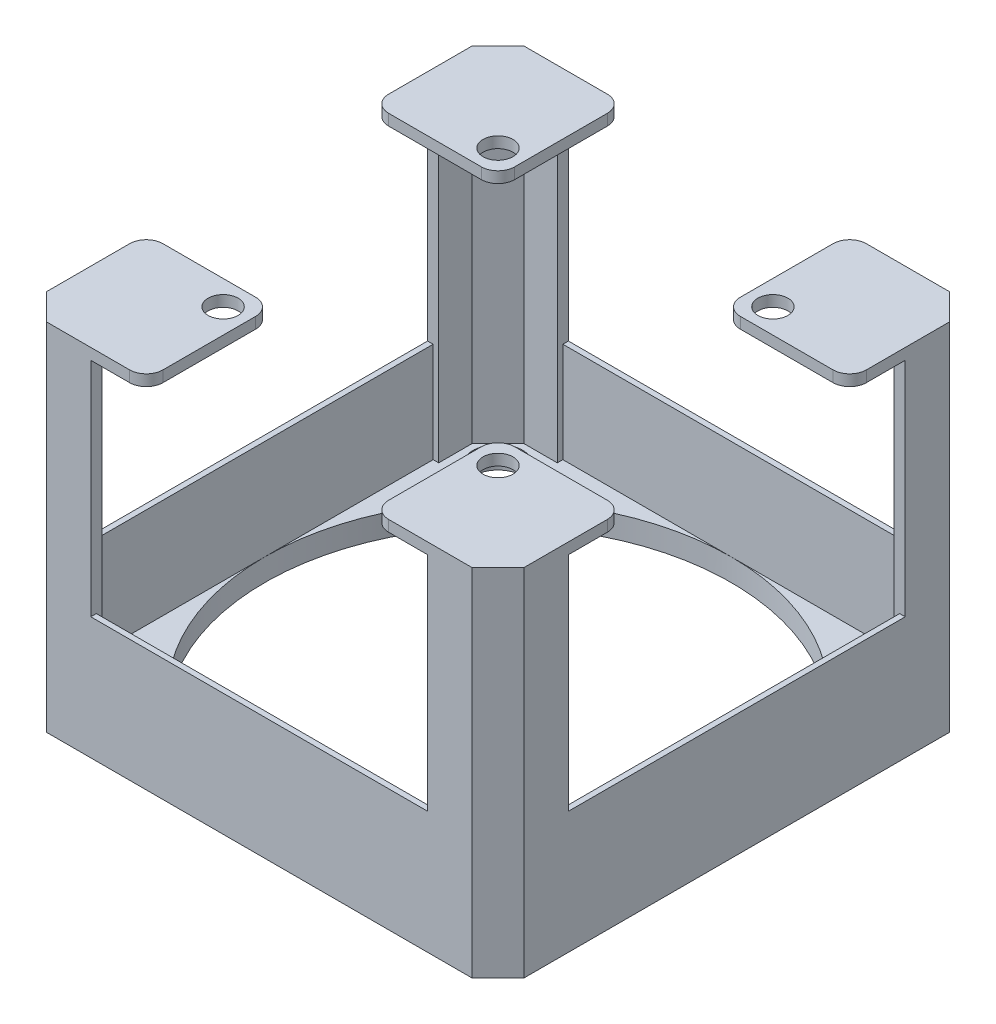
SolidWorks part; units mm, degrees
material "Wrought Stainless Steel"
ref_plane "Front Plane" through (0, 0, 0) normal (0, 0, 1) x (1, 0, 0)
ref_plane "Top Plane" through (0, 0, 0) normal (0, 1, 0) x (1, 0, 0)
ref_plane "Right Plane" through (0, 0, 0) normal (1, 0, 0) x (0, 0, -1)
sketch "Sketch1" plane through (0, 0, 0) normal (0, 1, 0) x (1, 0, 0)
  line L1 (0, 0) -> (38.3244, 0)
  line L2 (38.3244, 0) -> (40.6622, 2.3378)
  line L3 (40.6622, 2.3378) -> (40.6622, 40.6622)
  line L4 (40.6622, 40.6622) -> (38.3244, 43)
  line L5 (38.3244, 43) -> (0, 43)
  line L6 (0, 43) -> (-2.3378, 40.6622)
  line L7 (-2.3378, 40.6622) -> (-2.3378, 2.3378)
  line L8 (-2.3378, 2.3378) -> (0, 0)
  circle A0 centre (19.1622, 21.5) radius 21
extrude "Boss-Extrude1" add sketch "Sketch1" along normal blind 2 contours A0 | L8 L1 L2 L3 L4 L5 L6 L7 region at (19.1622, 0, -21.5)
sketch "Sketch3" plane through (0, 2, 0) normal (0, 1, 0) x (1, 0, 0)
  line L9 (0, 0) -> (38.3244, 0) construction
  line L10 (0, 0) -> (4, 0)
  line L11 (4, 0) -> (4, 1)
  line L12 (0, 0) -> (-2.3378, 2.3378)
  line L13 (-2.3378, 2.3378) -> (-2.3378, 6.3378)
  line L14 (38.3244, 43) -> (0, 43) construction
  line L15 (-2.3378, 36.6622) -> (-1.3378, 36.6622)
  line L16 (-1.3378, 36.6622) -> (-1.3378, 39.6622)
  line L17 (-1.3378, 39.6622) -> (1, 42)
  line L18 (1, 42) -> (4, 42)
  line L19 (40.6622, 2.3378) -> (40.6622, 40.6622) construction
  line L23 (37.3244, 42) -> (34.3244, 42)
  line L24 (38.3244, 0) -> (34.3244, 0)
  line L25 (34.3244, 0) -> (34.3244, 1)
  line L27 (40.6622, 36.6622) -> (39.6622, 36.6622)
  line L28 (39.6622, 36.6622) -> (39.6622, 39.6622)
  line L29 (4, 1) -> (1, 1)
  line L30 (-2.3378, 40.6622) -> (-2.3378, 2.3378) construction
  line L31 (-2.3378, 6.3378) -> (-1.3378, 6.3378)
  line L32 (-1.3378, 6.3378) -> (-1.3378, 3.3378)
  line L33 (-1.3378, 3.3378) -> (1, 1)
  line L34 (4, 42) -> (4, 43)
  line L35 (4, 43) -> (0, 43)
  line L36 (0, 43) -> (-2.3378, 40.6622)
  line L37 (-2.3378, 40.6622) -> (-2.3378, 36.6622)
  line L38 (34.3244, 42) -> (34.3244, 43)
  line L39 (34.3244, 43) -> (38.3244, 43)
  line L40 (38.3244, 43) -> (40.6622, 40.6622)
  line L41 (40.6622, 40.6622) -> (40.6622, 36.6622)
  line L42 (39.6622, 39.6622) -> (37.3244, 42)
  line L43 (34.3244, 1) -> (37.3244, 1)
  line L44 (37.3244, 1) -> (39.6622, 3.3378)
  line L45 (39.6622, 3.3378) -> (39.6622, 6.3378)
  line L46 (39.6622, 6.3378) -> (40.6622, 6.3378)
  line L47 (40.6622, 6.3378) -> (40.6622, 2.3378)
  line L48 (40.6622, 2.3378) -> (38.3244, 0)
  point P3 (19.1622, 0.5)
  point P4 (34.3244, 0)
  point P6 (40.1622, 21.5)
  point P7 (40.6622, 36.6622)
  point P8 (-2.3378, 40.6622)
  point P9 (19.1622, 42.5)
  point P10 (-2.3378, 36.6622)
  point P11 (0, 43)
  point P12 (-1.8378, 21.5)
  point P13 (-2.3378, 6.3378)
  point P14 (4, 0)
  point P21 (4, 43)
  point P24 (-2.3378, 2.3378)
  point P30 (38.3244, 0)
  line M3 (-2.3378, 40.6622) -> (-2.3378, 2.3378)
  line M4 (-2.3378, 2.3378) -> (0, 0)
  line M5 (0, 0) -> (38.3244, 0)
  line M6 (38.3244, 0) -> (40.6622, 2.3378)
  line M7 (40.6622, 2.3378) -> (40.6622, 40.6622)
  line M9 (38.3244, 43) -> (0, 43)
  line M10 (0, 43) -> (-2.3378, 40.6622)
extrude "Boss-Extrude6" add sketch "Sketch3" along normal blind 30 contours L46 L45 L44 L43 L25 M5 M6 M7 | L33 L32 L31 L11 L29 M3 M4 M5 | L18 L34 L15 L16 L17 M9 M10 M3 | L42 L23 L38 L39 L40 L41 L27 L28 region at (-1.1055, 2, -1.2323) region at (34.414, 2, -0.5) region at (-2.2482, 2, -38.6622)
sketch "Sketch13" plane through (0, 2, 0) normal (0, 1, 0) x (1, 0, 0)
  line L0 (4, 0.5) -> (34.3244, 0.5)
  line L1 (4, 0) -> (4, 1) construction
  line L2 (34.3244, 0) -> (34.3244, 1) construction
  line L3 (40.1622, 6.3378) -> (40.1622, 36.6622)
  line L4 (39.6622, 6.3378) -> (40.6622, 6.3378) construction
  line L5 (40.6622, 36.6622) -> (39.6622, 36.6622) construction
  line L6 (4, 42.5) -> (34.3244, 42.5)
  line L7 (4, 42) -> (4, 43) construction
  line L8 (34.3244, 42) -> (34.3244, 43) construction
  line L9 (-1.8378, 36.6622) -> (-1.8378, 6.3378)
  line L10 (-2.3378, 36.6622) -> (-1.3378, 36.6622) construction
  line L11 (-2.3378, 6.3378) -> (-1.3378, 6.3378) construction
  line L12 (-2.3378, 36.6622) -> (-2.3378, 6.3378)
  line L13 (4, 43) -> (34.3244, 43)
  line L14 (34.3244, 43) -> (4, 43)
  line L15 (4, 0) -> (34.3244, 0)
  line L16 (4, 0) -> (34.3244, 0) construction
  line L17 (40.6622, 36.6622) -> (40.6622, 6.3378)
  line M1 (40.6622, 36.6622) -> (39.6622, 36.6622)
  line M5 (34.3244, 42) -> (34.3244, 43)
  line M6 (34.3244, 43) -> (4, 43)
  line M7 (4, 43) -> (4, 42)
  line M11 (-1.3378, 36.6622) -> (-2.3378, 36.6622)
  line M12 (-2.3378, 36.6622) -> (-2.3378, 6.3378)
  line M13 (-2.3378, 6.3378) -> (-1.3378, 6.3378)
  line M17 (4, 1) -> (4, 0)
  line M18 (4, 0) -> (34.3244, 0)
  line M19 (34.3244, 0) -> (34.3244, 1)
  line M23 (39.6622, 6.3378) -> (40.6622, 6.3378)
  line M24 (40.6622, 6.3378) -> (40.6622, 36.6622)
extrude "Boss-Extrude7" add sketch "Sketch13" along normal blind 9 contours L0 M17 M18 M19 | L9 M11 M12 M13 | L3 M23 M24 M1 | L6 M7 M5 M6 region at (19.1622, 2, -0.25) region at (40.4122, 2, -21.5) region at (19.1622, 2, -42.75) region at (-2.0878, 2, -21.5)
sketch "Sketch15" plane through (0, 32, 0) normal (0, 1, 0) x (1, 0, 0)
  line L0 (19.1622, 21.5) -> (31.5366, 21.5)
  line L1 (31.5366, 21.5) -> (31.5366, 33.8744)
  line L2 (19.1622, 21.5) -> (19.1622, 9.1256)
  line L3 (19.1622, 9.1256) -> (6.7878, 9.1256)
  line L32 (4, 0) -> (7.5, 0)
  line L34 (-2.3378, 6.3378) -> (-2.3378, 9.8378)
  line L38 (4, 0) -> (0, 0)
  line L39 (0, 0) -> (-2.3378, 2.3378)
  line L40 (-2.3378, 2.3378) -> (-2.3378, 6.3378)
  line L41 (-0.8378, 11.3378) -> (7.5, 11.3378)
  line L42 (9, 9.8378) -> (9, 1.5)
  line L44 (39.1622, 11.3378) -> (30.8244, 11.3378)
  line L45 (40.6622, 6.3378) -> (40.6622, 9.8378)
  line L46 (40.6622, 2.3378) -> (40.6622, 6.3378)
  line L47 (38.3244, 0) -> (40.6622, 2.3378)
  line L48 (34.3244, 0) -> (38.3244, 0)
  line L49 (34.3244, 0) -> (30.8244, 0)
  line L50 (29.3244, 9.8378) -> (29.3244, 1.5)
  line L51 (-0.8378, 31.6622) -> (7.5, 31.6622)
  line L52 (-2.3378, 36.6622) -> (-2.3378, 33.1622)
  line L53 (-2.3378, 40.6622) -> (-2.3378, 36.6622)
  line L54 (0, 43) -> (-2.3378, 40.6622)
  line L55 (4, 43) -> (0, 43)
  line L56 (4, 43) -> (7.5, 43)
  line L57 (9, 33.1622) -> (9, 41.5)
  line L58 (40.6622, 36.6622) -> (40.6622, 33.1622)
  line L59 (40.6622, 40.6622) -> (40.6622, 36.6622)
  line L60 (38.3244, 43) -> (40.6622, 40.6622)
  line L61 (34.3244, 43) -> (38.3244, 43)
  line L62 (34.3244, 43) -> (30.8244, 43)
  line L63 (29.3244, 33.1622) -> (29.3244, 41.5)
  line L64 (39.1622, 31.6622) -> (30.8244, 31.6622)
  circle A0 centre (31.5366, 33.8744) radius 1.35
  circle A1 centre (6.7878, 9.1256) radius 1.35
  circle A2 centre (6.7878, 33.8744) radius 1.35
  circle A3 centre (31.5366, 9.1256) radius 1.35
  arc A11 (-2.3378, 9.8378) -> (-0.8378, 11.3378) centre (-0.8378, 9.8378) cw
  arc A12 (7.5, 0) -> (9, 1.5) centre (7.5, 1.5) ccw
  arc A13 (7.5, 11.3378) -> (9, 9.8378) centre (7.5, 9.8378) cw
  arc A14 (40.6622, 9.8378) -> (39.1622, 11.3378) centre (39.1622, 9.8378) ccw
  arc A15 (30.8244, 0) -> (29.3244, 1.5) centre (30.8244, 1.5) cw
  arc A16 (30.8244, 11.3378) -> (29.3244, 9.8378) centre (30.8244, 9.8378) ccw
  arc A17 (-2.3378, 33.1622) -> (-0.8378, 31.6622) centre (-0.8378, 33.1622) ccw
  arc A18 (7.5, 43) -> (9, 41.5) centre (7.5, 41.5) cw
  arc A19 (7.5, 31.6622) -> (9, 33.1622) centre (7.5, 33.1622) ccw
  arc A20 (40.6622, 33.1622) -> (39.1622, 31.6622) centre (39.1622, 33.1622) cw
  arc A21 (30.8244, 43) -> (29.3244, 41.5) centre (30.8244, 41.5) ccw
  arc A22 (30.8244, 31.6622) -> (29.3244, 33.1622) centre (30.8244, 33.1622) cw
  line M6 (39.6622, 39.6622) -> (39.6622, 36.6622)
  line M7 (39.6622, 36.6622) -> (40.6622, 36.6622)
  line M11 (34.3244, 43) -> (34.3244, 42)
  line M12 (34.3244, 42) -> (37.3244, 42)
  line M13 (37.3244, 42) -> (39.6622, 39.6622)
  dimension "D1" = 1.5
extrude "Boss-Extrude9" add sketch "Sketch15" against normal blind 1 contours A2 | L57 A20 L60 A0 M7 M6 M13 M12 M11 | L54 L50 A3 | L34 L40 L39 L38 L32 L47 A1 region at (34.697, 32, -37.0348) region at (3.2552, 32, -5.593) region at (35.0692, 32, -5.593) region at (3.2552, 32, -37.407)
sketch "Sketch16" plane through (0, 2, 0) normal (0, 1, 0) x (1, 0, 0)
  line L0 (19.1622, 21.5) -> (36.8399, 39.1777)
  line L1 (19.1622, 21.5) -> (36.8399, 3.8223)
  line L2 (19.1622, 21.5) -> (1.4845, 39.1777)
  line L3 (19.1622, 21.5) -> (1.4845, 3.8223)
  circle A0 centre (19.1622, 21.5) radius 25
  circle A1 centre (36.8399, 39.1777) radius 2.25
  circle A2 centre (36.8399, 3.8223) radius 2.25
  circle A3 centre (1.4845, 3.8223) radius 2.25
  circle A4 centre (1.4845, 39.1777) radius 2.25
extrude "Cut-Extrude1" cut sketch "Sketch16" against normal through all contours A4 | A1 | A2 | A3
